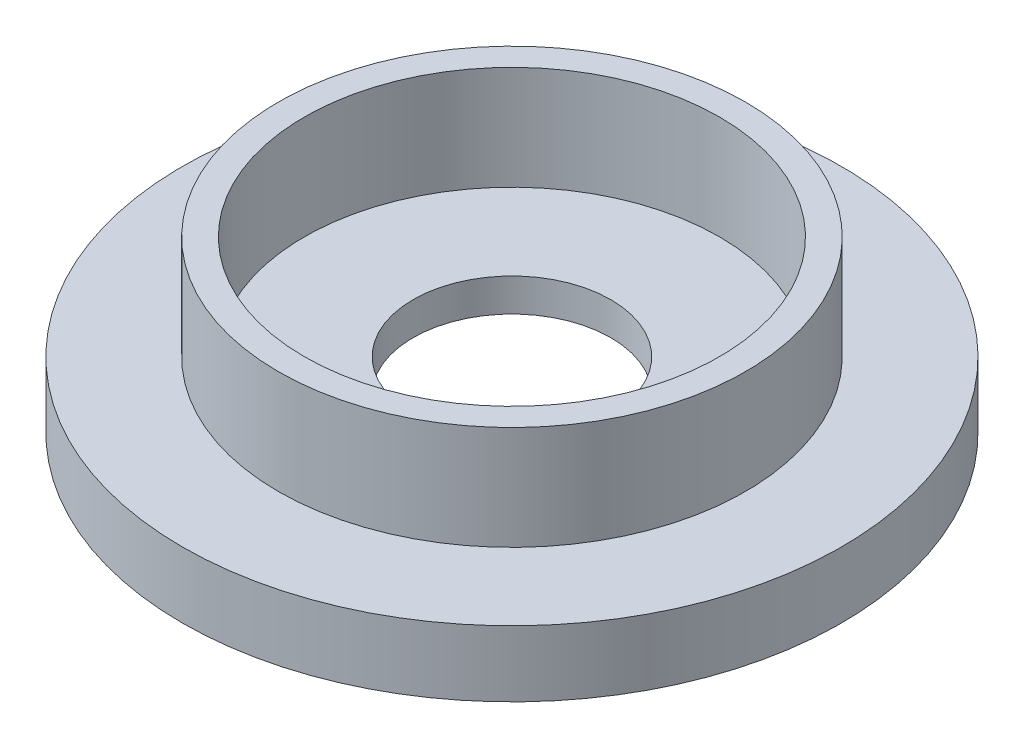
SolidWorks part; units mm, degrees
ref_plane "Front Plane" through (0, 0, 0) normal (0, 0, 1) x (1, 0, 0)
ref_plane "Top Plane" through (0, 0, 0) normal (0, 1, 0) x (1, 0, 0)
ref_plane "Right Plane" through (0, 0, 0) normal (1, 0, 0) x (0, 0, -1)
sketch "Sketch1" plane through (0, 0, 0) normal (0, 1, 0) x (1, 0, 0)
  circle A0 centre (0, 0) radius 63.5
  circle A1 centre (0, 0) radius 19.05
  dimension "D1" = 38.1
  dimension "D2" = 127
extrude "Boss-Extrude1" add sketch "Sketch1" along normal blind 12.7
sketch "Sketch2" plane through (0, 0, 0) normal (0, -1, 0) x (1, 0, 0)
  circle A0 centre (0, 0) radius 57.15
  circle A1 centre (0, 0) radius 63.5 construction
  dimension "D1" = 6.35
extrude "Cut-Extrude1" cut sketch "Sketch2" against normal blind 6.35
sketch "Sketch3" plane through (0, 12.7, 0) normal (0, 1, 0) x (1, 0, 0)
  circle A11 centre (0, 0) radius 40
  circle A12 centre (0, 0) radius 45
  dimension "D2" = 5
  dimension "D1" = 80
extrude "Boss-Extrude3" add sketch "Sketch3" along normal blind 20
ref_axis "CenterAxis" through (0, 34.335, 0) along (0, -1, 0)
